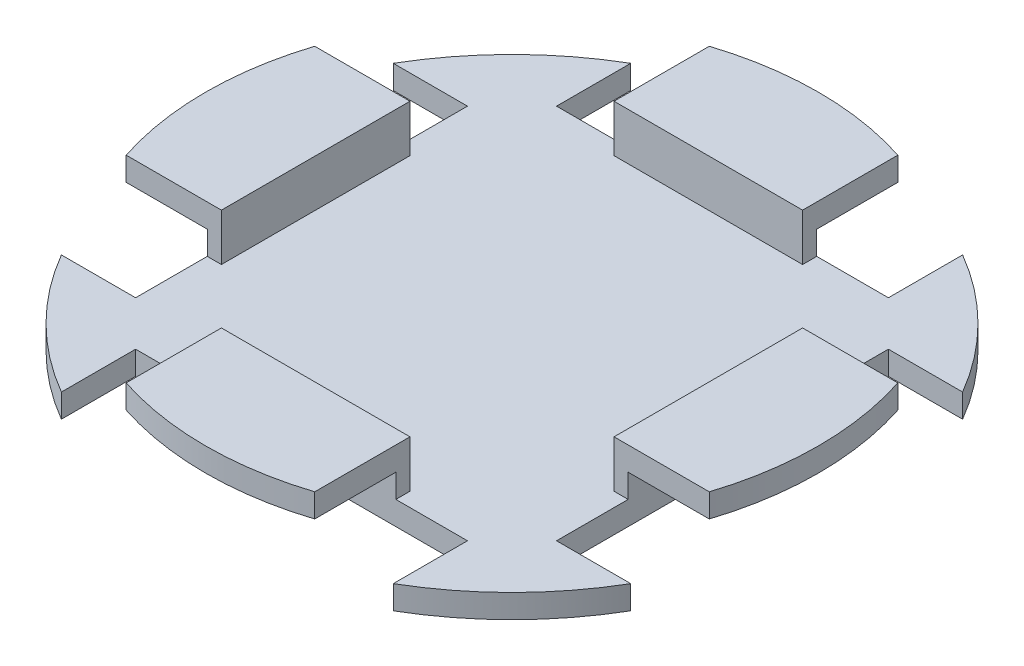
SolidWorks part; units mm, degrees
ref_plane "Front Plane" through (0, 0, 0) normal (0, 0, 1) x (1, 0, 0)
ref_plane "Top Plane" through (0, 0, 0) normal (0, 1, 0) x (1, 0, 0)
ref_plane "Right Plane" through (0, 0, 0) normal (1, 0, 0) x (0, 0, -1)
sketch "Sketch1" plane through (0, 0, 0) normal (0, 1, 0) x (1, 0, 0)
  circle A0 centre (0, 0) radius 88.773
  dimension "D1" = 177.546
extrude "Base" add sketch "Sketch1" along normal blind 6.35
sketch "Sketch2" plane through (0, 6.35, 0) normal (0, 1, 0) x (1, 0, 0)
  line L3 (0, 0) -> (0, -82.55) construction
  line L4 (-25.4, -78.5452) -> (-25.4, -52.8912)
  line L5 (-25.4, -52.8912) -> (0, -52.8912)
  line L6 (0, -52.8912) -> (25.4, -52.8912)
  line L7 (25.4, -52.8912) -> (25.4, -78.5452)
  arc A1 (25.4, -78.5452) -> (0, -82.55) centre (0, 0) cw
  arc A4 (-25.4, -78.5452) -> (0, -82.55) centre (0, 0) ccw
  circle A5 centre (0, 0) radius 88.773 construction
  point P2 (0, 0)
  point P5 (-6.3415, -52.4289)
  point P6 (0, -52.4289)
  point P8 (0, -82.55)
  point P9 (0, 0)
  point P13 (0, 0)
  point P14 (0, -52.4289)
  point P15 (0, 0)
  point P16 (0, 0)
  point P19 (0, 0)
  dimension "D3" = 82.55
  dimension "D1" = 25.4
  dimension "D2" = 25.654
extrude "Stopper" add sketch "Sketch2" along normal blind 12.7
sketch "Sketch5" plane through (0, 19.05, 0) normal (0, 1, 0) x (1, 0, 0)
  line L3 (0, 0) -> (0, -88.773) construction
  line L4 (-44.704, -76.6955) -> (-44.704, -56.7012)
  line L5 (-44.704, -56.7012) -> (0, -56.7012)
  line L6 (0, -56.7012) -> (44.704, -56.7012)
  line L7 (44.704, -56.7012) -> (44.704, -76.6955)
  line L8 (25.4, -78.5452) -> (25.4, -52.8912) construction
  line L9 (25.4, -52.8912) -> (-25.4, -52.8912) construction
  arc A1 (44.704, -76.6955) -> (0, -88.773) centre (0, 0) cw
  arc A4 (-44.704, -76.6955) -> (0, -88.773) centre (0, 0) ccw
  circle A7 centre (0, 0) radius 88.773 construction
  point P6 (0, -88.096)
  dimension "D1" = 3.81
  dimension "D2" = 19.304
extrude "Stopper Gap" cut sketch "Sketch5" along direction (0, -1, 0) on the side against the normal through all from offset 6.35 offset against normal yes
pattern_circular "CirPattern1" count 4 every 90 about axis through (0, 6.35, 0) along (0, 1, 0) of "Stopper Gap", "Stopper"
